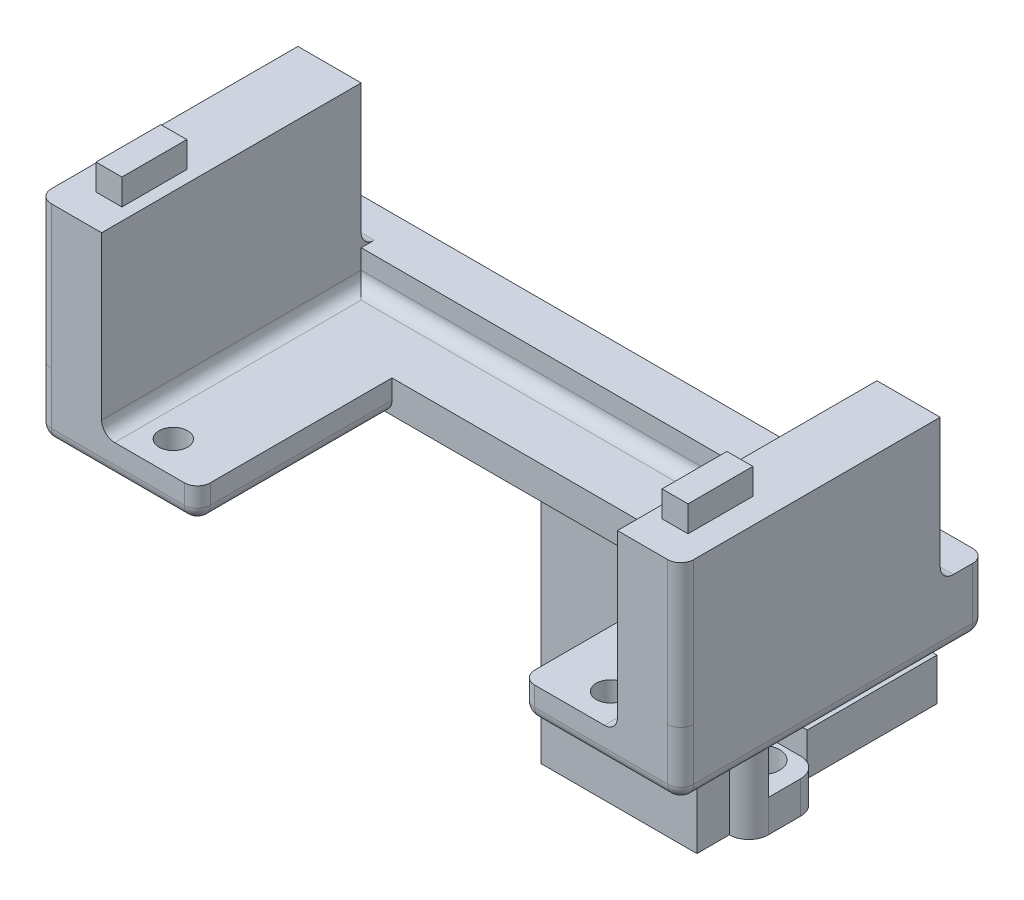
SolidWorks part; units mm, degrees
ref_plane "Front Plane" through (0, 0, 0) normal (0, 0, 1) x (1, 0, 0)
ref_plane "Top Plane" through (0, 0, 0) normal (0, 1, 0) x (1, 0, 0)
ref_plane "Right Plane" through (0, 0, 0) normal (1, 0, 0) x (0, 0, -1)
sketch "Sketch1" plane through (0, 0, 0) normal (0, 1, 0) x (1, 0, 0)
  line L1 (-18.5185, 2.5741) -> (11.4815, 2.5741)
  line L2 (-18.5185, 2.5741) -> (-18.5185, -8.4259)
  line L3 (-18.5185, -8.4259) -> (11.4815, -8.4259)
  line L4 (11.4815, 2.5741) -> (11.4815, -8.4259)
  circle A0 centre (-13.0185, -0.9259) radius 2.7
  circle A1 centre (5.9815, -0.9259) radius 2.75
  dimension "D3" = 5.4
  dimension "D4" = 5.5
  dimension "D5" = 7.5
  dimension "D6" = 7.5
  dimension "D7" = 19
  dimension "D8" = 5.5
  dimension "D9" = 5.5
  dimension "D1" = 30
  dimension "D2" = 11
extrude "Boss-Extrude1" add sketch "Sketch1" along normal blind 20 and the other way blind 30
sketch "Sketch2" plane through (0, 0, 8.4259) normal (0, 0, 1) x (1, 0, 0)
  line L0 (-18.5185, 20) -> (11.4815, 20) construction
  line L2 (-51.0185, 20) -> (-51.0185, 15)
  line L3 (-51.0185, 15) -> (43.9815, 15)
  line L4 (43.9815, 20) -> (43.9815, 15)
  line L5 (-51.0185, 20) -> (-51.0185, 25)
  line L6 (-51.0185, 25) -> (43.9815, 25)
  line L7 (43.9815, 25) -> (43.9815, 20)
  dimension "D1" = 5
  dimension "D2" = 95
  dimension "D3" = 32.5
extrude "Boss-Extrude4" add sketch "Sketch2" along normal blind 45
sketch "Sketch3" plane through (-51.0185, 0, 0) normal (-1, 0, 0) x (0, 0, 1)
  line L0 (8.4259, 25) -> (8.4259, 15) construction
  line L1 (53.4259, 15) -> (8.4259, 15)
  line L2 (53.4259, 15) -> (53.4259, 40)
  line L3 (53.4259, 40) -> (8.4259, 40)
  line L4 (8.4259, 15) -> (8.4259, 40)
  dimension "D1" = 25
  dimension "D2" = 0
extrude "Boss-Extrude5" add sketch "Sketch3" along normal blind 2
sketch "Sketch4" plane through (43.9815, 0, 0) normal (1, 0, 0) x (0, 0, -1)
  line L0 (-53.4259, 15) -> (-53.4259, 25) construction
  line L1 (-8.4259, 15) -> (-53.4259, 15)
  line L2 (-8.4259, 15) -> (-8.4259, 40)
  line L3 (-8.4259, 40) -> (-53.4259, 40)
  line L4 (-53.4259, 15) -> (-53.4259, 40)
  dimension "D1" = 0
  dimension "D2" = 25
extrude "Boss-Extrude6" add sketch "Sketch4" along normal blind 2
sketch "Sketch5" plane through (0, 0, 8.4259) normal (0, 0, -1) x (-1, 0, 0)
  line L1 (-45.9815, 40) -> (53.0185, 40)
  line L2 (-45.9815, 40) -> (-45.9815, 15)
  line L3 (-45.9815, 15) -> (53.0185, 15)
  line L4 (53.0185, 40) -> (53.0185, 15)
  dimension "D1" = 25
extrude "Boss-Extrude7" add sketch "Sketch5" along normal blind 2
fillet "Fillet1" radius 3 4 edges at (-18.5185, -7.5, 8.4259) (-18.5185, -5, -2.5741) (11.4815, -7.5, 8.4259) (11.4815, -5, -2.5741)
fillet "Fillet3" radius 2 4 edges at (45.9815, 15, 29.9259) (-53.0185, 15, 29.9259) (-53.0185, 27.5, 6.4259) (45.9815, 27.5, 6.4259)
fillet "Fillet4" radius 2 4 edges at (45.3957, 15.5858, 7.0117) (-52.4327, 15.5858, 7.0117) (27.6457, 15, 6.4259) (-34.6827, 15, 6.4259)
sketch "Sketch6" plane through (45.9815, 0, 0) normal (1, 0, 0) x (0, 0, -1)
  line L0 (-53.4259, 17) -> (-8.4259, 17) construction
  line L1 (3.773, 25) -> (-45.2259, 25)
  line L2 (3.773, 25) -> (3.773, 59)
  line L3 (3.773, 59) -> (-45.2259, 59)
  line L4 (-45.2259, 25) -> (-45.2259, 59)
  dimension "D1" = 34
  dimension "D2" = 8
extrude "Cut-Extrude1" cut sketch "Sketch6" against normal blind 10
sketch "Sketch7" plane through (0, 20, 0) normal (0, 1, 0) x (1, 0, 0)
  line L0 (-51.0185, -6.4259) -> (35.9815, -6.4259) construction
  line L1 (27.1444, 17.6917) -> (-30.2314, 17.6917)
  line L2 (27.1444, 17.6917) -> (27.1444, -5.4259)
  line L3 (27.1444, -5.4259) -> (-30.2314, -5.4259)
  line L4 (-30.2314, 17.6917) -> (-30.2314, -5.4259)
  dimension "D1" = 1
extrude "Cut-Extrude9" cut sketch "Sketch7" against normal blind 45
sketch "Sketch9" plane through (0, 0, -2.5741) normal (0, 0, -1) x (-1, 0, 0)
  line L0 (15.5185, -25) -> (-8.4815, -25) construction
  line L1 (-9.4815, -25) -> (16.5185, -25)
  line L2 (-9.4815, -25) -> (-9.4815, -27.5)
  line L3 (-9.4815, -27.5) -> (16.5185, -27.5)
  line L4 (16.5185, -25) -> (16.5185, -27.5)
  line L5 (-8.4815, -25) -> (-8.4815, -30) construction
  line L6 (15.5185, -30) -> (15.5185, -25) construction
  dimension "D1" = 0
  dimension "D2" = 2.5
  dimension "D3" = 1
  dimension "D4" = 1
  dimension "D5" = 26
extrude "Boss-Extrude8" add sketch "Sketch9" along normal blind 20
sketch "Sketch10" plane through (0, -25, 0) normal (0, 1, 0) x (1, 0, 0)
  line L0 (-14.5185, 20.5741) -> (7.4815, 20.5741)
  line L1 (7.4815, 20.5741) -> (7.4815, 4.5741)
  line L2 (7.4815, 4.5741) -> (-14.5185, 4.5741)
  line L3 (-14.5185, 4.5741) -> (-14.5185, 20.5741)
  line L4 (-16.5185, 22.5741) -> (9.4815, 22.5741) construction
  line L5 (-16.5185, 22.5741) -> (-16.5185, 2.5741) construction
  line L6 (9.4815, 22.5741) -> (9.4815, 2.5741) construction
  line L7 (-16.5185, 22.5741) -> (9.4815, 22.5741)
  line L8 (9.4815, 22.5741) -> (9.4815, 2.5741) construction
  line L9 (9.4815, 22.5741) -> (9.4815, 2.5741)
  line L10 (9.4815, 2.5741) -> (-16.5185, 2.5741)
  line L11 (-16.5185, 2.5741) -> (-16.5185, 22.5741)
  dimension "D1" = 2
  dimension "D2" = 2
  dimension "D3" = 2
  dimension "D4" = 16
  dimension "D5" = 20
extrude "Boss-Extrude9" add sketch "Sketch10" along normal blind 4
ref_plane "Plane1" through (0, 25, 0) normal (0, 1, 0) x (1, 0, 0)
sketch "Sketch12" plane through (0, 25, 0) normal (0, 1, 0) x (1, 0, 0)
  line L0 (0, 0) -> (98.1637, 0)
  line L1 (98.1637, 0) -> (98.1637, -70)
  line L2 (98.1637, -70) -> (-74.5554, -70)
  line L4 (-74.5554, 0) -> (0, 0)
  line L5 (-74.5554, 0) -> (-74.5554, -70)
extrude "Cut-Extrude10" cut sketch "Sketch12" along normal blind 20
sketch "Sketch13" plane through (0, 25, 0) normal (0, 1, 0) x (1, 0, 0)
  line L0 (-3.5185, -48.4259) -> (-3.5185, -53.4259)
  line L3 (-37.2185, -48.4259) -> (30.1815, -48.4259) construction
  line L4 (45.9815, -53.4259) -> (-53.0185, -53.4259) construction
  circle A0 centre (30.1815, -48.4259) radius 2.2
  circle A2 centre (-37.2185, -48.4259) radius 2.2
extrude "Cut-Extrude12" cut sketch "Sketch13" against normal blind 10 contours A2 | A0
fillet "Fillet5" radius 2 1 edges at (-53.0185, 21, 53.4259) type face fillet first side face at (-53.0185, 21, 30.9259) second side face at (4.7315, 18.8619, 53.4259)
sketch "Sketch15" plane through (0, 25, 0) normal (0, 1, 0) x (1, 0, 0)
  line L0 (-3.5185, -6.4259) -> (-3.5185, -53.4259) construction
  line L1 (43.9815, -6.4259) -> (-51.0185, -6.4259) construction
  line L2 (43.9815, -53.4259) -> (-51.0185, -53.4259) construction
  line L3 (-3.5185, -53.4259) -> (21.4815, -53.4259)
  line L4 (21.4815, -53.4259) -> (21.4815, -23.4259)
  line L5 (21.4815, -23.4259) -> (-28.5185, -23.4259)
  line L6 (-28.5185, -23.4259) -> (-28.5185, -53.4259)
  line L7 (-28.5185, -53.4259) -> (-3.5185, -53.4259)
extrude "Cut-Extrude13" cut sketch "Sketch15" against normal blind 10
fillet "Fillet8" radius 2 1 edges at (21.4815, 21, 53.4259) type face fillet first side face at (35.544, 21, 53.4259) second side face at (21.4815, 19.3172, 41.1088)
fillet "Fillet9" radius 2 1 edges at (-28.5185, 21, 53.4259) type face fillet first side face at (-36.956, 21, 53.4259) second side face at (-28.5185, 19.3172, 41.1088)
sketch "Sketch16" plane through (0, 25, 0) normal (0, 1, 0) x (1, 0, 0)
  line L0 (-40.7685, -53.4259) -> (-43.2685, -53.4259) construction
  line L1 (-30.5185, -53.4259) -> (-51.0185, -53.4259) construction
  line L2 (-43.2685, -53.4259) -> (-43.2685, -13.4259)
  line L3 (33.7315, -53.4259) -> (36.2315, -53.4259) construction
  line L4 (43.9815, -53.4259) -> (23.4815, -53.4259) construction
  line L5 (-43.2685, -13.4259) -> (36.2315, -13.4259)
  line L6 (36.2315, -13.4259) -> (36.2315, -53.4259)
  line L7 (36.2315, -53.4259) -> (-43.2685, -53.4259)
extrude "Cut-Extrude15" cut sketch "Sketch16" against normal blind 5
sketch "Sketch17" plane through (0, 25, 0) normal (0, 1, 0) x (1, 0, 0)
  line L0 (-43.2685, -53.4259) -> (-43.2685, -13.4259)
  line L1 (-43.2685, -13.4259) -> (-53.0185, -13.4259)
  line L2 (-53.0185, -8.4259) -> (-53.0185, -51.4259) construction
  line L3 (-53.0185, -13.4259) -> (-53.0185, -53.4259)
  line L4 (-53.0185, -53.4259) -> (-43.2685, -53.4259)
  line L5 (-3.5185, -23.4259) -> (-3.5185, -13.4259) construction
  line L6 (21.4815, -23.4259) -> (-28.5185, -23.4259) construction
  line L7 (36.2315, -13.4259) -> (-43.2685, -13.4259) construction
  line L8 (45.9815, -53.4259) -> (36.2315, -53.4259)
  line L9 (45.9815, -13.4259) -> (45.9815, -53.4259)
  line L10 (36.2315, -13.4259) -> (45.9815, -13.4259)
  line L11 (36.2315, -53.4259) -> (36.2315, -13.4259)
extrude "Boss-Extrude10" add sketch "Sketch17" along normal blind 22
fillet "Fillet12" radius 2 1 edges at (41.1065, 25, 13.4259) type face fillet first side face at (41.1065, 36, 13.4259) second side face at (-3.5185, 25, 10.3224)
fillet "Fillet13" radius 2 1 edges at (-48.1435, 25, 13.4259) type face fillet first side face at (0.8981, 25, 10.2228) second side face at (-48.1435, 36, 13.4259)
fillet "Fillet14" radius 2 1 edges at (-53.0185, 36, 53.4259) type face fillet first side face at (-53.0185, 28.2873, 29.4719) second side face at (-44.456, 27.25, 53.4259)
fillet "Fillet15" radius 2 1 edges at (45.9815, 36, 53.4259) type face fillet first side face at (45.9815, 28.2873, 29.4719) second side face at (37.419, 27.25, 53.4259)
fillet "Fillet17" radius 2 3 edges at (36.2315, 20, 33.4259) (-3.5185, 20, 13.4259) (-43.2685, 20, 33.4259) type face fillet first side face at (-3.5185, 20, 39.1088) second side face at (36.2315, 30.0837, 24.628) second side face at (-3.5185, 22.5, 13.4259) second side face at (-43.2685, 30.0837, 24.628)
sketch "Sketch19" plane through (0, 47, 0) normal (0, 1, 0) x (1, 0, 0)
  line L0 (-47.1435, -53.4259) -> (-47.1435, -48.4259) construction
  line L1 (-51.0185, -53.4259) -> (-43.2685, -53.4259) construction
  line L2 (-47.1435, -48.4259) -> (-45.1435, -48.4259)
  line L3 (-45.1435, -48.4259) -> (-45.1435, -38.4259)
  line L4 (-45.1435, -38.4259) -> (-49.1435, -38.4259)
  line L5 (-49.1435, -38.4259) -> (-49.1435, -48.4259)
  line L6 (-49.1435, -48.4259) -> (-47.1435, -48.4259)
  line L7 (36.2315, -53.4259) -> (40.1065, -53.4259) construction
  line L8 (36.2315, -53.4259) -> (43.9815, -53.4259) construction
  line L9 (40.1065, -53.4259) -> (40.1065, -48.4259) construction
  line L10 (40.1065, -48.4259) -> (42.1065, -48.4259)
  line L11 (42.1065, -48.4259) -> (42.1065, -38.4259)
  line L12 (42.1065, -38.4259) -> (38.1065, -38.4259)
  line L13 (38.1065, -38.4259) -> (38.1065, -48.4259)
  line L14 (38.1065, -48.4259) -> (40.1065, -48.4259)
extrude "Boss-Extrude11" add sketch "Sketch19" along normal blind 4
sketch "Sketch20" plane through (0, 0, 8.4259) normal (0, 0, 1) x (1, 0, 0)
  line L0 (-15.5185, -30) -> (-15.5185, 15)
  line L1 (-15.5185, 15) -> (8.4815, 15)
  line L2 (8.4815, 15) -> (8.4815, -30)
  line L3 (8.4815, -30) -> (-15.5185, -30)
extrude "Boss-Extrude12" add sketch "Sketch20" along normal blind 5
fillet "Fillet18" radius 5 1 edges at (-3.5185, 15, 13.4259) type face fillet first side face at (-3.5185, -7.5, 13.4259) second side face at (-37.2185, 15, 46.2259)
